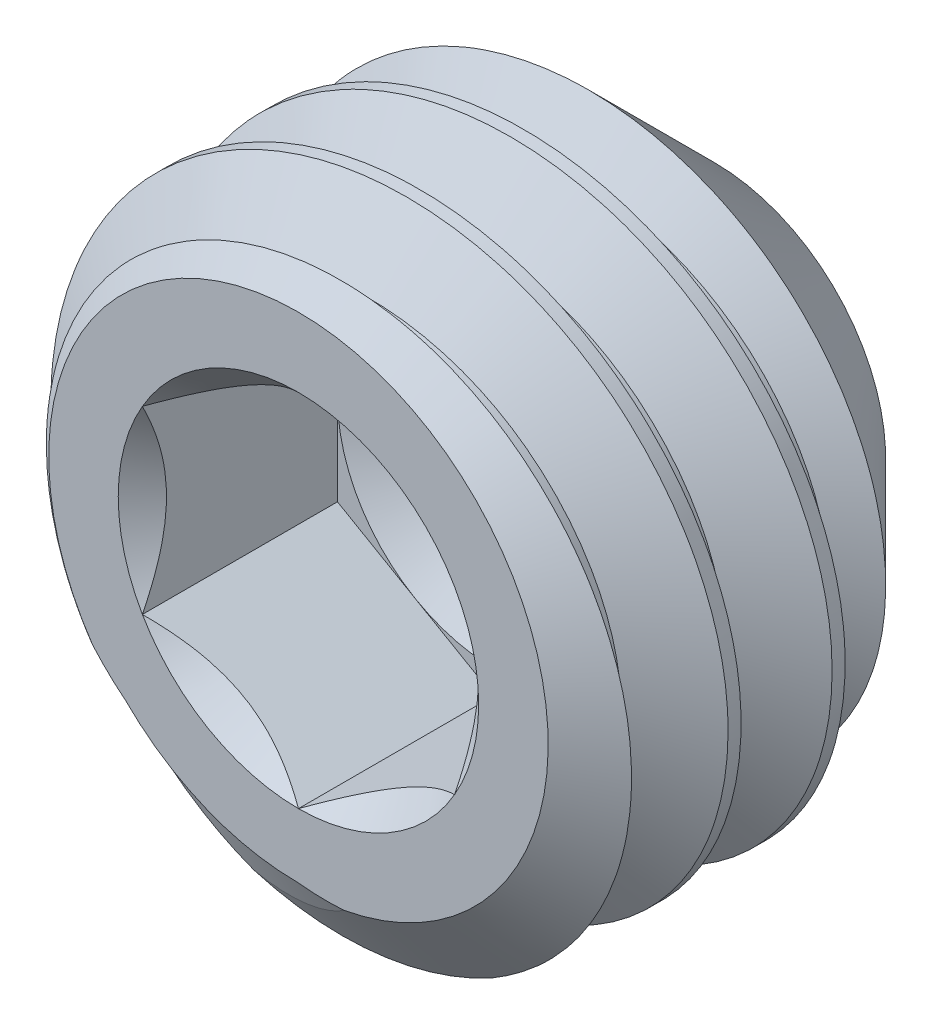
SolidWorks part; units mm, degrees
ref_plane "Front" through (0, 0, 0) normal (0, 0, 1) x (1, 0, 0)
ref_plane "Top" through (0, 0, 0) normal (0, 1, 0) x (1, 0, 0)
ref_plane "Right" through (0, 0, 0) normal (1, 0, 0) x (0, 0, -1)
sketch "Sketch22" plane through (0, 0, 0) normal (1, 0, 0) x (0, 0, -1)
  line L0 (-2.391, 0) -> (-2.391, 3.81)
  line L1 (-2.391, 3.81) -> (-1.724, 4.7625)
  line L2 (-1.724, 4.7625) -> (1.8062, 4.7625)
  line L3 (1.8062, 4.7625) -> (3.959, 2.6097)
  line L4 (3.959, 2.6097) -> (2.391, 0)
  line L5 (2.391, 0) -> (-2.391, 0)
  line L6 (2.391, 0) -> (3.959, 0) construction
  line L7 (3.959, 0) -> (3.959, 2.6097) construction
  line L8 (3.959, -2.6097) -> (2.391, 0) construction
  line L9 (-1.724, -4.7625) -> (1.8062, -4.7625) construction
  line L10 (3.959, -4.7625) -> (3.959, 4.7625) construction
  line L11 (3.959, 4.7625) -> (2.3715, 4.7625) construction
  point P11 (-0.0097, -4.7625)
  point P15 (3.959, 0)
  dimension "D3" = 35
  dimension "D5" = 118
  dimension "D6" = 45
  dimension "D7" = 7.62
  dimension "D1" = 3.9688
revolve "Revolve1" add sketch "Sketch22" angle 360 about L6
ref_plane "Plane1" through (0, 0, -3.959) normal (0, 0, 1) x (1, 0, 0)
sketch "Sketch27" plane through (0, 0, -3.959) normal (0, 0, 1) x (1, 0, 0)
  circle A0 centre (0, 0) radius 4.7625 construction
  circle A1 centre (0, 0) radius 4.7625
sketch "Sketch23" plane through (0, 0, 2.391) normal (0, 0, 1) x (1, 0, 0)
  line L1 (0, 2.7496) -> (-2.3813, 1.3748)
  line L2 (-2.3813, 1.3748) -> (-2.3813, -1.3748)
  line L3 (-2.3813, -1.3748) -> (0, -2.7496)
  line L4 (0, -2.7496) -> (2.3812, -1.3748)
  line L5 (2.3812, -1.3748) -> (2.3812, 1.3748)
  line L6 (2.3812, 1.3748) -> (0, 2.7496)
  circle A0 centre (0, 0) radius 2.3813 construction
extrude "Cut-Extrude10" cut sketch "Sketch23" against normal blind 2.9766
sketch "Sketch24" plane through (0, 0, 2.391) normal (0, 0, 1) x (1, 0, 0)
  circle A0 centre (0, 0) radius 2.7496
extrude "Cut-Extrude11" cut sketch "Sketch24" against normal through all draft 45
sketch "Sketch26" plane through (0, 0, -0.5856) normal (0, 0, 1) x (1, 0, 0)
  circle A0 centre (0, 0) radius 2.3813 construction
  circle A1 centre (0, 0) radius 2.3813
extrude "Cut-Extrude12" cut sketch "Sketch26" against normal through all draft 60
sketch "Sketch31" plane through (0, 0, 0) normal (1, 0, 0) x (0, 0, -1)
  line L2 (2.391, 0) -> (3.959, -2.6097)
  line L3 (3.959, 2.6097) -> (2.391, 0)
ref_axis "Center Axis1" through (0, 0, -42.9554) along (0, 0, 1)
ref_plane "Contact Plane1" through (0, 0, -3.959) normal (0, 0, 1) x (1, 0, 0)
ref_plane "Contact Plane2" through (0, 0, 2.391) normal (0, 0, 1) x (1, 0, 0)
curve "Helix/Spiral1" pitch 1.5875 height 7.9375 radius 4.7625 centre (0, 0, -3.959) axis (0, 0, 1) start towards (0, 1, 0)
sketch "Sketch32" plane through (0, 0, 0) normal (1, 0, 0) x (0, 0, -1)
  line L0 (3.8598, 4.9344) -> (5.4473, 4.9344) construction
  line L1 (5.4473, 4.9344) -> (4.6536, 3.5595) construction
  line L2 (4.6536, 3.5595) -> (3.8598, 4.9344) construction
  line L3 (3.959, 4.7625) -> (2.3715, 4.7625) construction
  line L4 (4.6536, 3.5595) -> (4.6536, 3.7314) construction
  line L5 (4.6536, 4.9344) -> (4.6536, 4.7625) construction
  line L6 (4.5543, 3.7314) -> (4.7528, 3.7314)
  line L7 (3.959, 4.7625) -> (5.3481, 4.7625) construction
  line L8 (3.9094, 4.8484) -> (5.3977, 4.8484)
  line L9 (3.9094, 4.8484) -> (4.5543, 3.7314)
  line L10 (4.7528, 3.7314) -> (5.3977, 4.8484)
  point P11 (4.6536, 3.7314)
  point P13 (4.6536, 4.7625)
  point P17 (4.6536, 4.8484)
  dimension "D1" = 0.1984
sweep "Cut-Sweep1" cut profiles "Sketch32" path "Helix/Spiral1"
equation "\"D7@Sketch22\"=\"Dia@Sketch22\"*.8"
equation "\"D3@Helix/Spiral1\"=\"Length@Sketch22\" + \"Pitch@Sketch22\"l1\""
equation "\"hex Depth@Cut-Extrude10\" = \"Hex@Sketch23\" * .625"
equation "\"D1@Sketch22\"=\"Pitch@Sketch22\"*2.5"
equation "\"D4@Helix/Spiral1\"=\"Pitch@Sketch22\""
equation "\"D1@Sketch32\"=\"Pitch@Sketch22\"*.125"
